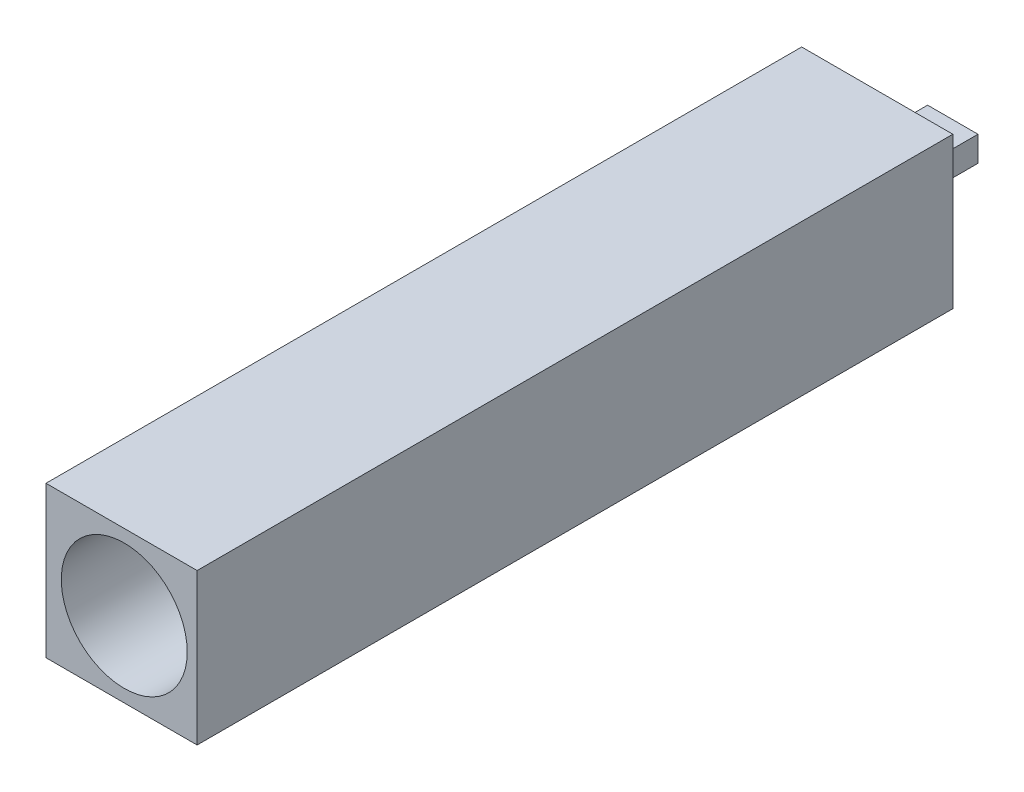
SolidWorks part; units mm, degrees
material "1345 Alloy"
ref_plane "Front Plane" through (0, 0, 0) normal (0, 0, 1) x (1, 0, 0)
ref_plane "Top Plane" through (0, 0, 0) normal (0, 1, 0) x (1, 0, 0)
ref_plane "Right Plane" through (0, 0, 0) normal (1, 0, 0) x (0, 0, -1)
sketch "Sketch1" plane through (0, 0, 0) normal (0, 0, 1) x (1, 0, 0)
  line L1 (0, 0) -> (-30, 0)
  line L2 (0, 0) -> (0, 30)
  line L3 (0, 30) -> (-30, 30)
  line L4 (-30, 0) -> (-30, 30)
  dimension "D1" = 30
  dimension "D2" = 30
extrude "Boss-Extrude1" add sketch "Sketch1" along normal blind 150
sketch "Sketch2" plane through (0, 0, 150) normal (0, 0, 1) x (1, 0, 0)
  line L0 (0, 30) -> (-30, 30) construction
  circle A0 centre (-14.4685, 15) radius 12.5
  dimension "D1" = 25
  dimension "D2" = 15
extrude "Cut-Extrude1" cut sketch "Sketch2" against normal blind 120 contours A0
sketch "Sketch3" plane through (0, 0, 0) normal (0, 0, -1) x (-1, 0, 0)
  line L0 (0, 30) -> (30, 30) construction
  line L1 (20, 12.5) -> (10, 12.5)
  line L2 (20, 12.5) -> (20, 17.5)
  line L3 (20, 17.5) -> (10, 17.5)
  line L4 (10, 12.5) -> (10, 17.5)
  line L5 (30, 30) -> (30, 0) construction
  dimension "D1" = 10
  dimension "D2" = 5
  dimension "D3" = 12.5
  dimension "D4" = 10
extrude "Boss-Extrude2" add sketch "Sketch3" along normal blind 15
sketch "Sketch4" plane through (0, 12.5, 0) normal (0, -1, 0) x (1, 0, 0)
  line L0 (-10, -15) -> (-20, -15) construction
  line L1 (-20, -15) -> (-20, 0) construction
  circle A0 centre (-15, -10) radius 2.5
  dimension "D1" = 5
  dimension "D2" = 5
  dimension "D3" = 5
extrude "Cut-Extrude2" cut sketch "Sketch4" against normal blind 10
ref_axis "Axis1" through (-15, 40.3616, -10) along (0, -1, 0)
